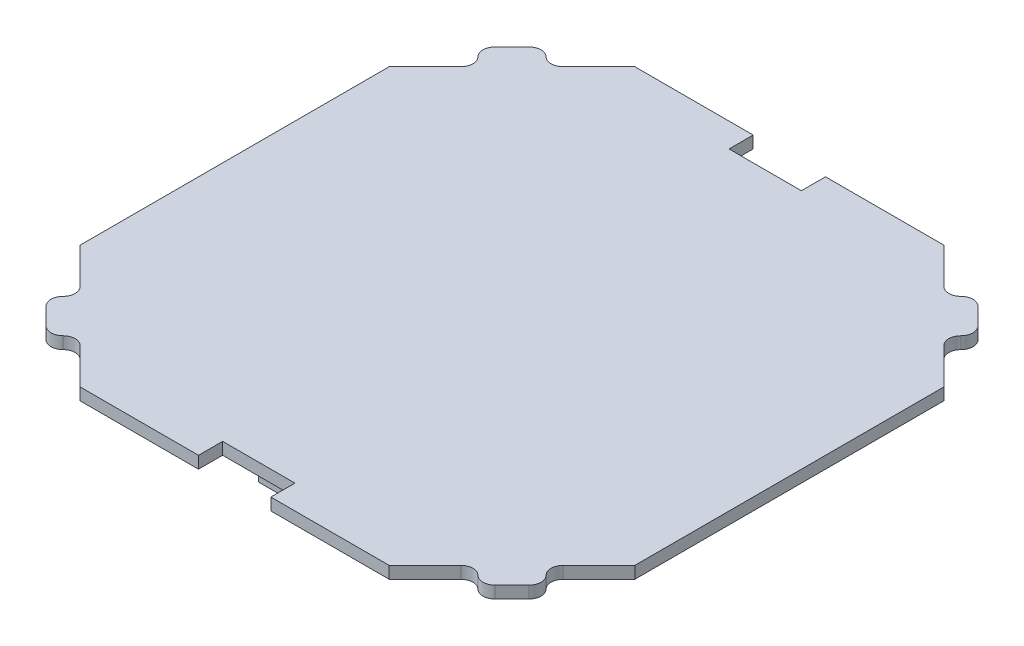
SolidWorks part; units mm, degrees
ref_plane "Płaszczyzna przednia" through (0, 0, 0) normal (0, 0, 1) x (1, 0, 0)
ref_plane "Płaszczyzna górna" through (0, 0, 0) normal (0, 1, 0) x (1, 0, 0)
ref_plane "Płaszczyzna prawa" through (0, 0, 0) normal (1, 0, 0) x (0, 0, -1)
sketch "Szkic1" plane through (0, 0, 0) normal (0, 1, 0) x (1, 0, 0)
  line L1 (-115, 115) -> (115, 115)
  line L2 (-115, 115) -> (-115, -115)
  line L3 (-115, -115) -> (115, -115)
  line L4 (115, 115) -> (115, -115)
  line L5 (-115, 115) -> (115, -115) construction
  line L6 (-115, -115) -> (115, 115) construction
  point P0 (0, 0)
  dimension "D1" = 230
  dimension "100" = 230
extrude "Dodanie-wyciągnięcie1" add sketch "Szkic1" along normal blind 5
sketch "Szkic2" plane through (0, 5, 0) normal (0, 1, 0) x (1, 0, 0)
  line L0 (-115, 115) -> (-64.0883, 115)
  line L1 (115, 115) -> (-115, 115) construction
  line L2 (-64.0883, 115) -> (-82.4731, 96.6152)
  line L3 (-82.4731, 96.6152) -> (-89.5442, 103.6863)
  line L4 (-89.5442, 103.6863) -> (-103.6863, 89.5442)
  line L5 (-103.6863, 89.5442) -> (-96.6152, 82.4731)
  line L6 (-96.6152, 82.4731) -> (-115, 64.0883)
  line L7 (-115, 115) -> (-115, -115) construction
  line L8 (-115, 64.0883) -> (-115, 115)
  dimension "D1" = 20
  dimension "D2" = 26
  dimension "D3" = 26
  dimension "D4" = 10
extrude "Wytnij-wyciągnięcie1" cut sketch "Szkic2" against normal through all both and the other way through all
fillet "Zaokrąglenie2" radius 5 4 edges at (-82.4731, 2.5, -96.6152) (-89.5442, 2.5, -103.6863) (-103.6863, 2.5, -89.5442) (-96.6152, 2.5, -82.4731)
ref_axis "Oś1" through (0, 5.25, 0) along (0, -1, 0)
pattern_circular "Szyk kołowy1" count 4 every 90 about axis through (0, 5.25, 0) along (0, -1, 0) of "Zaokrąglenie2", "Wytnij-wyciągnięcie1"
sketch "Szkic3" plane through (0, 5, 0) normal (0, 1, 0) x (1, 0, 0)
  line L0 (0, 0) -> (0, -110) construction
  line L2 (-15, -105) -> (-15, -115)
  line L3 (-15, -105) -> (15, -105)
  line L4 (-15, -115) -> (15, -115)
  line L5 (15, -105) -> (15, -115)
  line L6 (-15, -105) -> (15, -115) construction
  line L7 (-15, -115) -> (15, -105) construction
  line L9 (-64.0883, -115) -> (64.0883, -115) construction
  point P2 (0, -115)
  dimension "D1" = 110
  dimension "D2" = 30
extrude "Wytnij-wyciągnięcie2" cut sketch "Szkic3" against normal through all
mirror "Lustro1" about plane through (0, 0, 0) normal (0, 0, 1) of "Wytnij-wyciągnięcie2"
sketch "Szkic4" plane through (0, 0, 0) normal (0, -1, 0) x (1, 0, 0)
  line L6 (-10, 0) -> (10, 0) construction
  line L7 (-10.2279, 95) -> (10.2279, 95)
  line L8 (-10.2279, 95) -> (-10.2279, -95)
  line L9 (10.2279, 95) -> (10.2279, -95)
  line L10 (-10.2279, -95) -> (10.2279, -95)
  line L11 (-10.2279, 95) -> (10.2279, -95) construction
  line L12 (10.2279, 95) -> (-10.2279, -95) construction
  line L13 (15, 105) -> (-15, 105) construction
  point P3 (0, 0)
  point P4 (0, 0)
  dimension "D1" = 20
  dimension "D2" = 10
extrude "Dodanie-wyciągnięcie2" add sketch "Szkic4" along normal blind 5
sketch "Szkic5" plane through (0, -5, 0) normal (0, -1, 0) x (1, 0, 0)
  line L1 (10.2279, -95) -> (7.2279, -95)
  line L2 (10.2279, -95) -> (10.2279, -85)
  line L3 (10.2279, -85) -> (7.2279, -85)
  line L4 (-10.2279, -95) -> (-10.2279, -85)
  line L5 (7.2279, -95) -> (7.2279, -85)
  line L6 (-7.2279, -95) -> (-7.2279, -85)
  line L7 (7.2279, -85) -> (-7.2279, -85) construction
  line L8 (-7.2279, -85) -> (-10.2279, -85)
  line L9 (7.2279, -95) -> (-7.2279, -95) construction
  line L10 (-7.2279, -95) -> (-10.2279, -95)
  point P5 (-10.2279, -95)
  point P11 (15, -95)
  point P12 (10.2279, -95)
  point P14 (-15, -95)
  dimension "D1" = 10
  dimension "D2" = 3
  dimension "D3" = 3
extrude "Dodanie-wyciągnięcie3" add sketch "Szkic5" along normal blind 4.25
sketch "Szkic6" plane through (0, -9.25, 0) normal (0, -1, 0) x (1, 0, 0)
  line L0 (10.2279, -95) -> (10.2279, 95) construction
  line L1 (-10.2279, -95) -> (10.2279, -95)
  line L2 (-10.2279, -95) -> (-10.2279, -84.9686)
  line L3 (-10.2279, -84.9686) -> (10.2279, -84.9686)
  line L4 (10.2279, -95) -> (10.2279, -84.9686)
  point P6 (-10.2279, -95)
  point P8 (10.2279, -84.9686)
extrude "Dodanie-wyciągnięcie4" add sketch "Szkic6" along normal blind 3
pattern_linear "Szyk liniowy1" count 8 spacing 25.7 along (0, 0, 1) of "Dodanie-wyciągnięcie4", "Dodanie-wyciągnięcie3"
